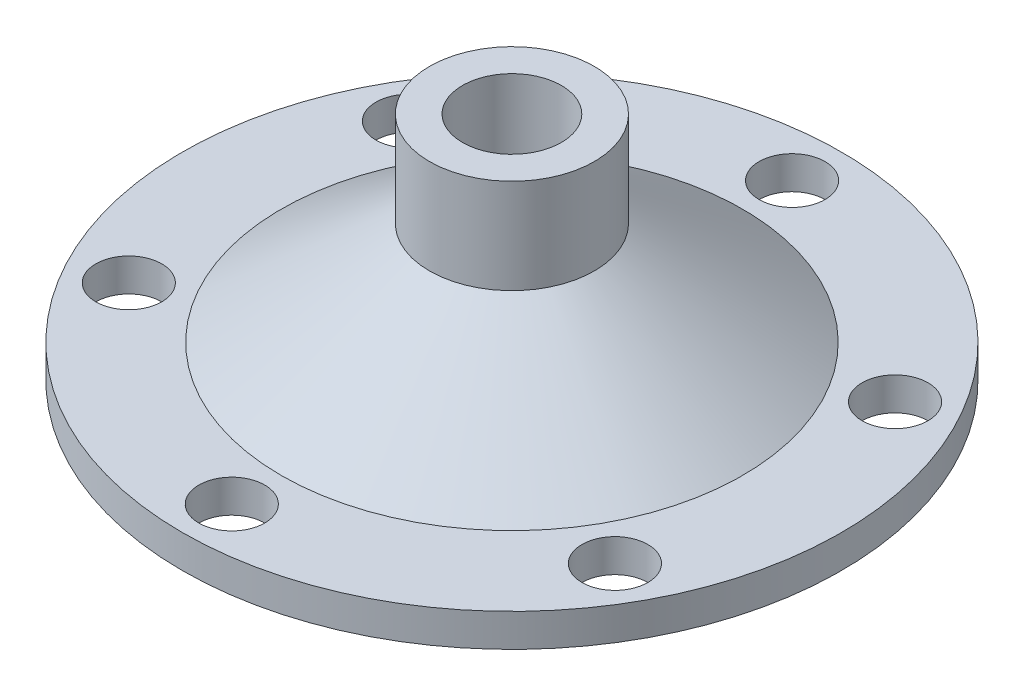
SolidWorks part; units mm, degrees
ref_plane "Front Plane" through (0, 0, 0) normal (0, 0, 1) x (1, 0, 0)
ref_plane "Top Plane" through (0, 0, 0) normal (0, 1, 0) x (1, 0, 0)
ref_plane "Right Plane" through (0, 0, 0) normal (1, 0, 0) x (0, 0, -1)
sketch "Sketch1" plane through (0, 0, 0) normal (0, 1, 0) x (1, 0, 0)
  circle A0 centre (0, 0) radius 127
extrude "Boss-Extrude1" add sketch "Sketch1" along normal blind 12.7
sketch "Sketch2" plane through (0, 12.7, 0) normal (0, 1, 0) x (1, 0, 0)
  circle A0 centre (0, 107.95) radius 12.7
  circle A1 centre (0, -107.95) radius 12.7
  circle A2 centre (-93.6625, 53.975) radius 12.7
  circle A3 centre (93.6625, 53.975) radius 12.7
  circle A4 centre (-93.6625, -53.975) radius 12.7
  circle A5 centre (93.6625, -53.975) radius 12.7
  dimension "D1" = 25.4
  dimension "D2" = 93.6625
  dimension "D3" = 53.975
  dimension "D4" = 53.975
  dimension "D5" = 93.6625
  dimension "D6" = 53.975
  dimension "D7" = 93.6625
  dimension "D8" = 53.975
  dimension "D9" = 93.6625
  dimension "D10" = 107.95
  dimension "D11" = 107.95
extrude "Cut-Extrude2" cut sketch "Sketch2" against normal blind 12.7
sketch "Sketch4" plane through (0, 12.7, 0) normal (0, 1, 0) x (1, 0, 0)
  circle A0 centre (0, 0) radius 88.9
extrude "Boss-Extrude2" add sketch "Sketch4" along normal blind 39.6875
chamfer "Chamfer2" distance 39.6875 angle 55.21 1 edges at (0, 52.3875, 88.9) first distance on face at (0, 52.3875, 88.9)
sketch "Sketch6" plane through (0, 52.3875, 0) normal (0, 1, 0) x (1, 0, 0)
  circle A0 centre (0, 0) radius 31.7759
extrude "Boss-Extrude3" add sketch "Sketch6" along normal blind 36.5125
sketch "Sketch7" plane through (0, 88.9, 0) normal (0, 1, 0) x (1, 0, 0)
  circle A0 centre (0, 0) radius 19.05
extrude "Cut-Extrude3" cut sketch "Sketch7" against normal blind 155.3845
